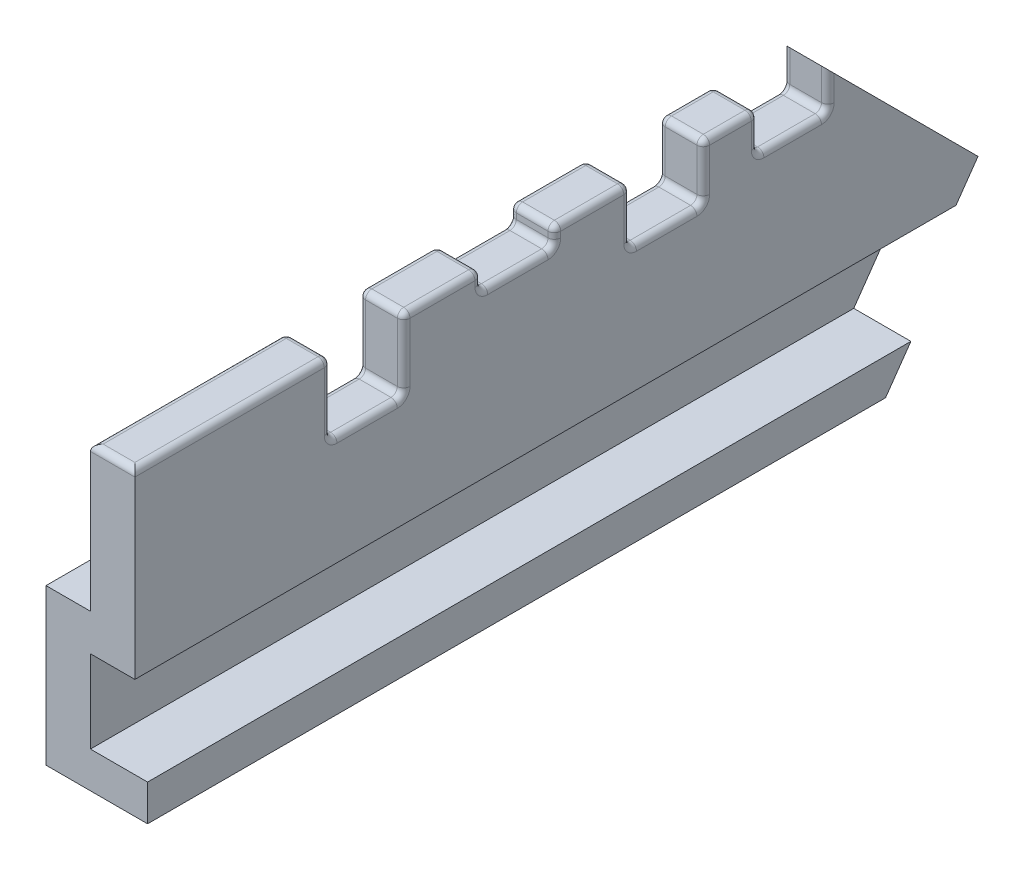
SolidWorks part; units mm, degrees
note: The reader was unsure of these and kept them because the rebuilt part matched: shared geometry of "3DSketch1<3>", "3DSketch1<4>", "3DSketch1<5>".
ref_plane "Front Plane" through (0, 0, 0) normal (0, 0, 1) x (1, 0, 0)
ref_plane "Top Plane" through (0, 0, 0) normal (0, 1, 0) x (1, 0, 0)
ref_plane "Right Plane" through (0, 0, 0) normal (1, 0, 0) x (0, 0, -1)
sketch "Sketch1" plane through (0, 0, 0) normal (0, 0, 1) x (1, 0, 0)
  line L0 (0, 3.8362) -> (0, -3.8362) construction
  line L1 (0, 0) -> (0, 2.28)
  line L2 (0, 2.28) -> (0.7, 2.28)
  line L3 (0.7, 2.28) -> (0.7, -0.58)
  line L4 (0.7, -0.58) -> (0, -0.58)
  line L5 (0, -0.58) -> (0, -1.88)
  line L6 (0.9, -1.88) -> (0, -1.88)
  line L7 (0.9, -1.88) -> (0.9, -2.45)
  line L8 (0.9, -2.45) -> (-0.7, -2.45)
  line L9 (-0.7, -2.45) -> (-0.7, 0)
  line L10 (-0.7, 0) -> (0, 0)
  dimension "D1" = 0.7
  dimension "D2" = 2.86
  dimension "D3" = 1.3
  dimension "D4" = 2.45
  dimension "D5" = 4.73
  dimension "D6" = 1.6
  dimension "D7" = 0.7
extrude "Boss-Extrude1" add sketch "Sketch1" along normal blind 13.28
sketch "Sketch2" plane through (0, 0, 0) normal (1, 0, 0) x (0, 0, -1)
  line L0 (-6.64, 2.28) -> (-6.64, -2.45) construction
  line L1 (-13.28, 2.28) -> (0, 2.28) construction
  line L2 (-13.28, -2.45) -> (0, -2.45) construction
  line L3 (-6.64, -0.085) -> (-13.7893, -0.085) construction
  line L4 (-13.28, -0.085) -> (-10.615, 2.58) construction
  line L5 (-13.28, -0.58) -> (-13.28, 2.28) construction
  line L6 (-10.615, 2.58) -> (-14.08, 2.58) construction
  line L7 (-14.08, 2.58) -> (-14.08, -0.085) construction
  line L8 (-13.28, -0.085) -> (-11.4139, -2.75) construction
  line L9 (-11.4139, -2.75) -> (-14.08, -2.75) construction
  line L10 (-14.08, -2.75) -> (-14.08, -0.085) construction
  line L11 (0.8, -2.75) -> (0.8, -0.085)
  line L12 (-1.8661, -2.75) -> (0.8, -2.75)
  line L13 (0, -0.085) -> (-1.8661, -2.75)
  line L14 (0.8, 2.58) -> (0.8, -0.085)
  line L15 (-2.665, 2.58) -> (0.8, 2.58)
  line L16 (0, -0.085) -> (-2.665, 2.58)
  dimension "D1" = 45
  dimension "D2" = 55
  dimension "D3" = 0.3
  dimension "D4" = 0.3
  dimension "D5" = 0.8
extrude "Cut-Extrude1" cut sketch "Sketch2" against normal through all both and the other way through all
sketch3d "3DSketch1"
  line L0 (0, 2.28, 13.28) -> (0, 2.28, 2.365) construction
  line L1 (0.0493, 2.28, 13.28) -> (0.0493, 2.28, 3.48) construction
  line L2 (0, 2.28, 10.1964) -> (0, 2.28, 9.0464)
  line L3 (0, 2.28, 10.1964) -> (0.7, 2.28, 10.1964)
  line L4 (0.7, 2.28, 10.1964) -> (0.7, 2.28, 9.0464)
  line L5 (0, 2.28, 9.0464) -> (0.7, 2.28, 9.0464)
  line L6 (0.2936, 2.28, 13.28) -> (0.2936, 2.28, 10.25) construction
  line L7 (0.7, 2.28, 13.28) -> (0, 2.28, 13.28) construction
  line L8 (0.5055, 2.28, 13.28) -> (0.5055, 2.28, 7.81) construction
  line L9 (0.1317, 2.28, 13.28) -> (0.1317, 2.28, 5.48) construction
  line L10 (0.7, 2.28, 13.28) -> (0.7, 2.28, 2.365) construction
  line L12 (0.7, 2.28, 7.8225) -> (0.7, 2.28, 6.6725)
  line L13 (0.7, 2.28, 7.8225) -> (0, 2.28, 7.8225)
  line L14 (0, 2.28, 7.8225) -> (0, 2.28, 6.6725)
  line L15 (0.7, 2.28, 6.6725) -> (0, 2.28, 6.6725)
  line L16 (0, 2.28, 5.4786) -> (0, 2.28, 4.3268)
  line L17 (0, 2.28, 5.4786) -> (0.7, 2.28, 5.4786)
  line L18 (0.7, 2.28, 5.4786) -> (0.7, 2.28, 4.3268)
  line L19 (0, 2.28, 4.3268) -> (0.7, 2.28, 4.3268)
  line L20 (0, 2.28, 3.4712) -> (0, 2.28, 2.365)
  line L21 (0, 2.28, 3.4712) -> (0.7, 2.28, 3.4712)
  line L22 (0.7, 2.28, 3.4712) -> (0.7, 2.28, 2.365)
  line L23 (0, 2.28, 2.365) -> (0.7, 2.28, 2.365)
extrude "Cut-Extrude5" cut sketch "3DSketch1" along direction (0, -1, 0) on the side against the normal blind 0.29 contours L13 L14 L15 L12
extrude "Cut-Extrude6" cut sketch "3DSketch1<3>" against normal blind 1.13 contours L2 L5 L4 L3
sketch3d "3DSketch1<3>" same geometry as "3DSketch1"
extrude "Cut-Extrude7" cut sketch "3DSketch1<4>" against normal blind 0.87 contours L19 L18 L17 L16
sketch3d "3DSketch1<4>" same geometry as "3DSketch1"
extrude "Cut-Extrude8" cut sketch "3DSketch1<5>" against normal blind 0.6 contours L20 L23 L22 L21
sketch3d "3DSketch1<5>" same geometry as "3DSketch1"
fillet "Fillet1" radius 0.1 32 edges at (0.35, 2.28, 13.28)
